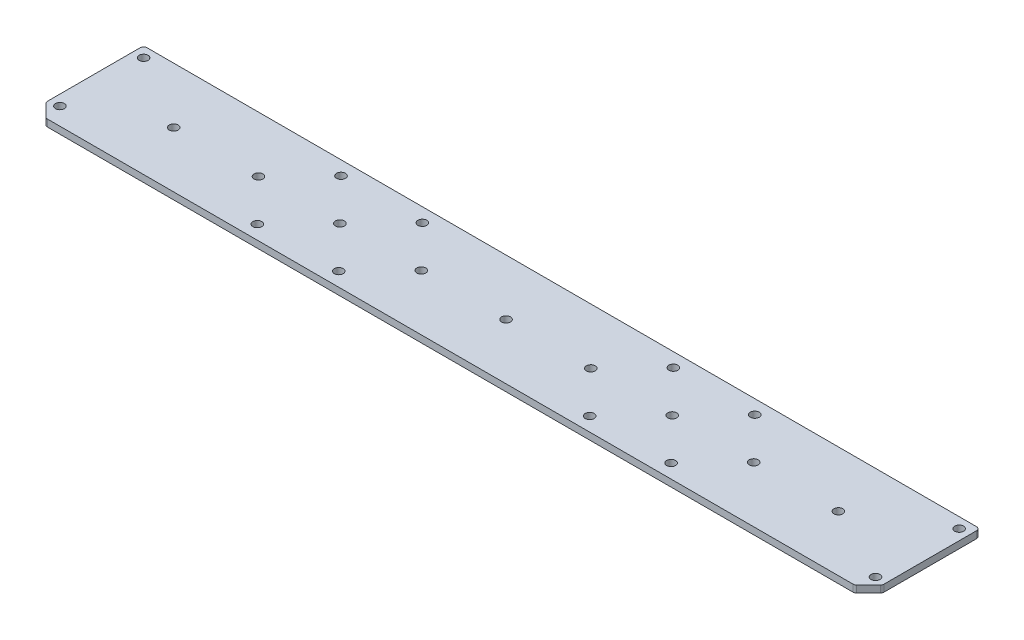
SolidWorks part; units mm, degrees
ref_plane "Front Plane" through (0, 0, 0) normal (0, 0, 1) x (1, 0, 0)
ref_plane "Top Plane" through (0, 0, 0) normal (0, 1, 0) x (1, 0, 0)
ref_plane "Right Plane" through (0, 0, 0) normal (1, 0, 0) x (0, 0, -1)
sketch "Sketch2" plane through (0, 0, 0) normal (0, 1, 0) x (1, 0, 0)
  line L0 (0, 7.0076) -> (0, 50.8)
  line L1 (0, 50.8) -> (381, 50.8)
  line L2 (381, 50.8) -> (381, 7.0076)
  line L3 (373.9924, 0) -> (7.0076, 0)
  line L4 (5.885, 0.465) -> (0.465, 5.885) construction
  line L5 (5.885, 0.465) -> (0.465, 5.885)
  line L6 (375.115, 0.465) -> (380.535, 5.885) construction
  line L7 (375.115, 0.465) -> (380.535, 5.885)
  line L8 (336.7191, 50.8) -> (379.4125, 50.8) construction
  arc A0 (5.885, 0.465) -> (7.0076, 0) centre (7.0076, 1.5875) ccw construction
  arc A1 (0, 7.0076) -> (0.465, 5.885) centre (1.5875, 7.0076) ccw construction
  arc A2 (5.885, 0.465) -> (7.0076, 0) centre (7.0076, 1.5875) ccw
  arc A3 (0, 7.0076) -> (0.465, 5.885) centre (1.5875, 7.0076) ccw
  arc A4 (373.9924, 0) -> (375.115, 0.465) centre (373.9924, 1.5875) ccw construction
  arc A6 (373.9924, 0) -> (375.115, 0.465) centre (373.9924, 1.5875) ccw
  arc A8 (380.535, 5.885) -> (381, 7.0076) centre (379.4125, 7.0076) ccw construction
  arc A9 (380.535, 5.885) -> (381, 7.0076) centre (379.4125, 7.0076) ccw
extrude "Boss-Extrude1" add sketch "Sketch2" along normal blind 3.175
sketch "Sketch3" plane through (0, 0, 0) normal (0, 1, 0) x (1, 0, 0)
  circle A25 centre (4.7625, 7.9375) radius 2.032 construction
  circle A31 centre (4.7625, 46.0375) radius 2.032 construction
  circle A63 centre (376.2375, 7.9375) radius 2.032 construction
  circle A64 centre (376.2375, 46.0375) radius 2.032 construction
  circle A67 centre (4.7625, 7.9375) radius 2.032
  circle A68 centre (4.7625, 46.0375) radius 2.032
  circle A72 centre (376.2375, 7.9375) radius 2.032
  circle A73 centre (376.2375, 46.0375) radius 2.032
  circle A123 centre (341.884, 25.4) radius 2.032 construction
  circle A124 centre (247.65, 44.45) radius 2.032 construction
  circle A125 centre (284.734, 44.45) radius 2.032 construction
  circle A128 centre (247.65, 6.35) radius 2.032 construction
  circle A129 centre (284.734, 6.35) radius 2.032 construction
  circle A132 centre (190.5, 25.4) radius 2.032 construction
  circle A134 centre (170.434, 6.35) radius 2.032 construction
  circle A135 centre (133.35, 44.45) radius 2.032 construction
  circle A136 centre (96.266, 44.45) radius 2.032 construction
  circle A137 centre (96.266, 6.35) radius 2.032 construction
  circle A140 centre (77.724, 25.4) radius 2.032 construction
  circle A141 centre (39.116, 25.4) radius 2.032 construction
  circle A142 centre (341.884, 25.4) radius 2.032
  circle A143 centre (247.65, 44.45) radius 2.032
  circle A144 centre (284.734, 44.45) radius 2.032
  circle A147 centre (247.65, 6.35) radius 2.032
  circle A148 centre (284.734, 6.35) radius 2.032
  circle A151 centre (190.5, 25.4) radius 2.032
  circle A154 centre (133.35, 44.45) radius 2.032
  circle A155 centre (96.266, 44.45) radius 2.032
  circle A156 centre (96.266, 6.35) radius 2.032
  circle A159 centre (77.724, 25.4) radius 2.032
  circle A160 centre (39.116, 25.4) radius 2.032
  circle A161 centre (151.892, 25.4) radius 2.032
  circle A162 centre (229.108, 25.4) radius 2.032
  circle A163 centre (266.192, 25.4) radius 2.032
  circle A164 centre (303.276, 25.4) radius 2.032
  circle A165 centre (151.892, 25.4) radius 2.3813 construction
  circle A166 centre (229.108, 25.4) radius 2.3813 construction
  circle A167 centre (266.192, 25.4) radius 2.3813 construction
  circle A168 centre (303.276, 25.4) radius 2.3813 construction
  circle A169 centre (133.35, 6.35) radius 2.032
  circle A170 centre (114.808, 25.4) radius 2.032 construction
  circle A171 centre (114.808, 25.4) radius 2.032
extrude "Cut-Extrude1" cut sketch "Sketch3" along normal through all
fillet "Fillet1" radius 1.5875 2 edges at (0, 1.5875, -50.8) (381, 1.5875, -50.8)
